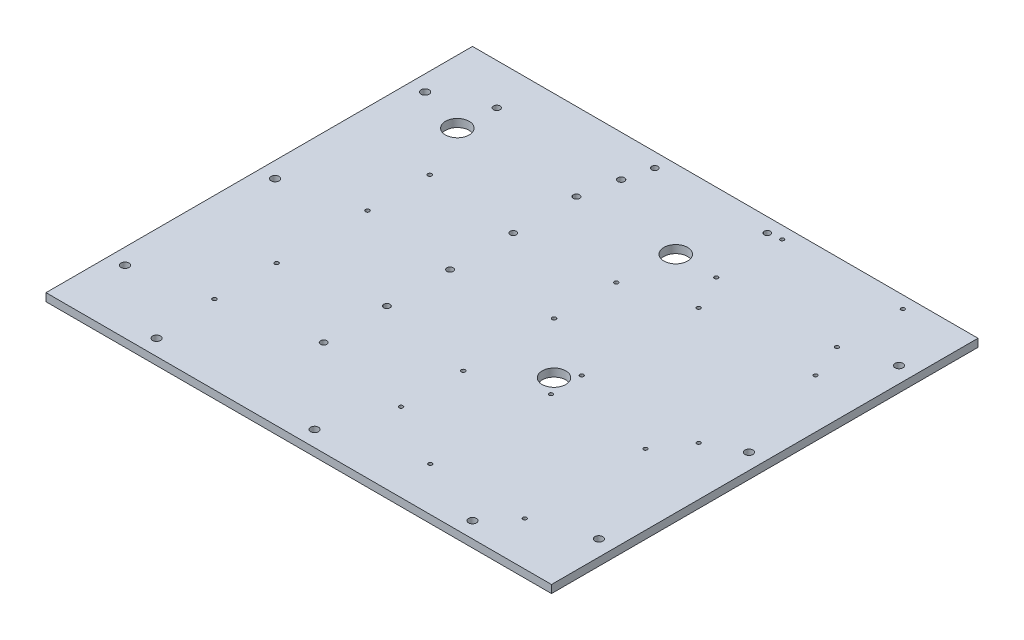
SolidWorks part; units mm, degrees
ref_plane "Front Plane" through (0, 0, 0) normal (0, 0, 1) x (1, 0, 0)
ref_plane "Top Plane" through (0, 0, 0) normal (0, 1, 0) x (1, 0, 0)
ref_plane "Right Plane" through (0, 0, 0) normal (1, 0, 0) x (0, 0, -1)
sketch "Sketch1" plane through (0, 0, 0) normal (0, 1, 0) x (1, 0, 0)
  line L0 (406.4, 0) -> (406.4, 342.9) construction
  line L1 (0, 0) -> (406.4, 0)
  line L2 (0, 0) -> (0, 342.9)
  line L3 (0, 342.9) -> (406.4, 342.9)
  line L4 (406.4, 0) -> (406.4, 342.9)
  line L5 (406.4, 0) -> (406.4, 342.9) construction
  line L6 (387.3669, 342.9) -> (384.1496, 342.9) construction
  line L7 (387.3669, 342.9) -> (384.1496, 342.9) construction
  point P9 (0, 0)
extrude "Boss-Extrude1" add sketch "Sketch1" along normal blind 6.35
sketch "Sketch3" plane through (0, 6.35, 0) normal (0, 1, 0) x (1, 0, 0)
  line L0 (0, 342.9) -> (0, 0) construction
  line L1 (25.4, 25.4) -> (381, 25.4) construction
  line L2 (25.4, 25.4) -> (25.4, 317.5) construction
  line L3 (25.4, 317.5) -> (381, 317.5) construction
  line L4 (381, 25.4) -> (381, 317.5) construction
  line L5 (0, 0) -> (406.4, 0) construction
  line L6 (406.4, 0) -> (406.4, 342.9) construction
  line L7 (406.4, 342.9) -> (0, 342.9) construction
  line L8 (0, 171.45) -> (406.4, 171.45) construction
  line L9 (203.2, 0) -> (203.2, 342.9) construction
  line L10 (12.7, 342.9) -> (12.7, 0) construction
  line L11 (393.7, 342.9) -> (393.7, 0) construction
  line L12 (406.4, 12.7) -> (0, 12.7) construction
  line L13 (12.7, 292.1) -> (393.7, 292.1) construction
  line L14 (12.7, 50.8) -> (393.7, 50.8) construction
  circle A0 centre (203.2, 12.7) radius 3.175
  circle A1 centre (330.2, 12.7) radius 3.175
  circle A2 centre (76.2, 12.7) radius 3.175
  circle A3 centre (12.7, 171.45) radius 3.175
  circle A4 centre (393.7, 171.45) radius 3.175
  circle A5 centre (12.7, 292.1) radius 3.175
  circle A6 centre (12.7, 50.8) radius 3.175
  circle A7 centre (393.7, 50.8) radius 3.175
  circle A8 centre (393.7, 292.1) radius 3.175
  dimension "D8" = 6.35
  dimension "D1" = 25.4
  dimension "D2" = 25.4
  dimension "D3" = 25.4
  dimension "D4" = 25.4
  dimension "D5" = 12.7
  dimension "D6" = 12.7
  dimension "D7" = 12.7
  dimension "D9" = 76.2
  dimension "D10" = 76.2
  dimension "D11" = 50.8
  dimension "D12" = 50.8
extrude "Cut-Extrude1" cut sketch "Sketch3" against normal through all
sketch "Sketch4" plane through (0, 6.35, 0) normal (0, 1, 0) x (1, 0, 0)
  line L0 (406.4, 342.9) -> (0, 342.9) construction
  line L1 (406.4, 0) -> (406.4, 342.9) construction
  line L2 (203.2, 342.9) -> (203.2, 0) construction
  line L3 (0, 0) -> (406.4, 0) construction
  line L4 (226.4, 279.9) -> (50.8, 279.9) construction
  line L5 (0, 342.9) -> (0, 0) construction
  line L6 (0, 342.9) -> (0, 0) construction
  line L7 (157.3728, 309.88) -> (147.7068, 309.88) construction
  line L8 (47.7068, 309.88) -> (57.3728, 309.88) construction
  line L9 (147.7068, 312.547) -> (157.3728, 312.547) construction
  line L10 (47.7068, 312.547) -> (57.3728, 312.547) construction
  line L11 (146.3548, 284.861) -> (146.3548, 275.336) construction
  line L12 (146.3548, 275.336) -> (146.3548, 234.061) construction
  line L13 (146.3548, 234.061) -> (146.3548, 224.536) construction
  line L14 (146.3548, 224.536) -> (146.3548, 183.261) construction
  line L15 (146.3548, 183.261) -> (146.3548, 173.736) construction
  line L16 (146.3548, 173.736) -> (146.3548, 132.461) construction
  line L17 (146.3548, 132.461) -> (146.3548, 122.936) construction
  line L18 (146.3548, 122.936) -> (146.3548, 81.661) construction
  line L19 (146.3548, 81.661) -> (146.3548, 72.136) construction
  line L20 (406.4, 0) -> (406.4, 342.9) construction
  circle A0 centre (226.4, 279.9) radius 9.525
  circle A1 centre (50.8, 279.9) radius 9.525
  circle A2 centre (222.1748, 63.265) radius 1.5875 construction
  circle A3 centre (222.1748, 113.265) radius 1.5875 construction
  circle A4 centre (72.1748, 113.265) radius 1.5875 construction
  circle A5 centre (72.1748, 63.265) radius 1.5875 construction
  circle A6 centre (72.1748, 186.295) radius 1.5875 construction
  circle A7 centre (72.1748, 236.295) radius 1.5875 construction
  circle A8 centre (222.1748, 236.295) radius 1.5875 construction
  circle A9 centre (222.1748, 186.295) radius 1.5875 construction
  circle A10 centre (222.1748, 63.265) radius 1.5875
  circle A11 centre (222.1748, 113.265) radius 1.5875
  circle A12 centre (72.1748, 113.265) radius 1.5875
  circle A13 centre (72.1748, 63.265) radius 1.5875
  circle A14 centre (72.1748, 186.295) radius 1.5875
  circle A15 centre (72.1748, 236.295) radius 1.5875
  circle A16 centre (222.1748, 236.295) radius 1.5875
  circle A17 centre (222.1748, 186.295) radius 1.5875
  circle A18 centre (355.833, 333.05) radius 1.5 construction
  circle A19 centre (258.833, 333.05) radius 1.5 construction
  circle A20 centre (355.833, 280.05) radius 1.5 construction
  circle A21 centre (258.833, 280.05) radius 1.5 construction
  circle A22 centre (248.4501, 331.47) radius 2.5 construction
  circle A23 centre (157.9499, 331.47) radius 2.5 construction
  circle A24 centre (366.9502, 251.78) radius 1.5 construction
  circle A25 centre (272.9502, 251.78) radius 1.5 construction
  circle A26 centre (366.9502, 157.78) radius 1.5 construction
  circle A27 centre (272.9502, 157.78) radius 1.5 construction
  circle A28 centre (248.4501, 331.47) radius 2.5
  circle A29 centre (157.9499, 331.47) radius 2.5
  arc A30 (47.7068, 312.547) -> (47.7068, 307.213) centre (47.7068, 309.88) ccw construction
  arc A31 (57.3728, 307.213) -> (57.3728, 312.547) centre (57.3728, 309.88) ccw construction
  arc A32 (147.7068, 312.547) -> (147.7068, 307.213) centre (147.7068, 309.88) ccw construction
  arc A33 (157.3728, 307.213) -> (157.3728, 312.547) centre (157.3728, 309.88) ccw construction
  arc A34 (47.7068, 312.547) -> (47.7068, 307.213) centre (47.7068, 309.88) ccw construction
  arc A35 (57.3728, 307.213) -> (57.3728, 312.547) centre (57.3728, 309.88) ccw construction
  arc A36 (147.7068, 312.547) -> (147.7068, 307.213) centre (147.7068, 309.88) ccw construction
  arc A37 (157.3728, 307.213) -> (157.3728, 312.547) centre (157.3728, 309.88) ccw construction
  circle A38 centre (52.5398, 309.88) radius 2.667
  circle A39 centre (152.5398, 309.88) radius 2.667
  arc A40 (148.8948, 81.661) -> (143.8148, 81.661) centre (146.3548, 81.661) ccw construction
  arc A41 (143.8148, 72.136) -> (148.8948, 72.136) centre (146.3548, 72.136) ccw construction
  arc A42 (143.8148, 122.936) -> (148.8948, 122.936) centre (146.3548, 122.936) ccw construction
  arc A43 (148.8948, 132.461) -> (143.8148, 132.461) centre (146.3548, 132.461) ccw construction
  arc A44 (143.8148, 173.736) -> (148.8948, 173.736) centre (146.3548, 173.736) ccw construction
  arc A45 (148.8948, 183.261) -> (143.8148, 183.261) centre (146.3548, 183.261) ccw construction
  arc A46 (143.8148, 224.536) -> (148.8948, 224.536) centre (146.3548, 224.536) ccw construction
  arc A47 (148.8948, 234.061) -> (143.8148, 234.061) centre (146.3548, 234.061) ccw construction
  arc A48 (143.8148, 275.336) -> (148.8948, 275.336) centre (146.3548, 275.336) ccw construction
  arc A49 (148.8948, 284.861) -> (143.8148, 284.861) centre (146.3548, 284.861) ccw construction
  arc A50 (148.8948, 81.661) -> (143.8148, 81.661) centre (146.3548, 81.661) ccw construction
  arc A51 (143.8148, 72.136) -> (148.8948, 72.136) centre (146.3548, 72.136) ccw construction
  arc A52 (143.8148, 122.936) -> (148.8948, 122.936) centre (146.3548, 122.936) ccw construction
  arc A53 (148.8948, 132.461) -> (143.8148, 132.461) centre (146.3548, 132.461) ccw construction
  arc A54 (143.8148, 173.736) -> (148.8948, 173.736) centre (146.3548, 173.736) ccw construction
  arc A55 (148.8948, 183.261) -> (143.8148, 183.261) centre (146.3548, 183.261) ccw construction
  arc A56 (143.8148, 224.536) -> (148.8948, 224.536) centre (146.3548, 224.536) ccw construction
  arc A57 (148.8948, 234.061) -> (143.8148, 234.061) centre (146.3548, 234.061) ccw construction
  arc A58 (143.8148, 275.336) -> (148.8948, 275.336) centre (146.3548, 275.336) ccw construction
  arc A59 (148.8948, 284.861) -> (143.8148, 284.861) centre (146.3548, 284.861) ccw construction
  circle A60 centre (146.3548, 178.4985) radius 2.54
  circle A61 centre (146.3548, 127.6985) radius 2.54
  circle A62 centre (146.3548, 76.8985) radius 2.54
  circle A63 centre (146.3548, 280.0985) radius 2.54
  circle A64 centre (146.3548, 229.2985) radius 2.54
  circle A65 centre (349.7002, 35.25) radius 1.5 construction
  circle A66 centre (349.7002, 132.25) radius 1.5 construction
  circle A67 centre (273.7002, 132.25) radius 1.5 construction
  circle A68 centre (273.7002, 35.25) radius 1.5 construction
  circle A69 centre (355.833, 333.05) radius 1.5
  circle A70 centre (258.833, 333.05) radius 1.5
  circle A71 centre (355.833, 280.05) radius 1.5
  circle A72 centre (258.833, 280.05) radius 1.5
  circle A73 centre (366.9502, 251.78) radius 1.5
  circle A74 centre (272.9502, 251.78) radius 1.5
  circle A75 centre (366.9502, 157.78) radius 1.5
  circle A76 centre (272.9502, 157.78) radius 1.5
  circle A77 centre (349.7002, 35.25) radius 1.5
  circle A78 centre (349.7002, 132.25) radius 1.5
  circle A79 centre (273.7002, 132.25) radius 1.5
  circle A80 centre (273.7002, 35.25) radius 1.5
  circle A81 centre (263.4, 145) radius 9.525
  point P39 (0, 0)
  point P143 (263.3888, 145.2847)
  dimension "D1" = 19.05
  dimension "D6" = 19.05
  dimension "D2" = 63
  dimension "D3" = 180
  dimension "D4" = 342.9
  dimension "D5" = 50.8
  dimension "D7" = 143
  dimension "D8" = 145
extrude "Cut-Extrude2" cut sketch "Sketch4" against normal through all
equation "\"D9@Sketch3\"=3in"
